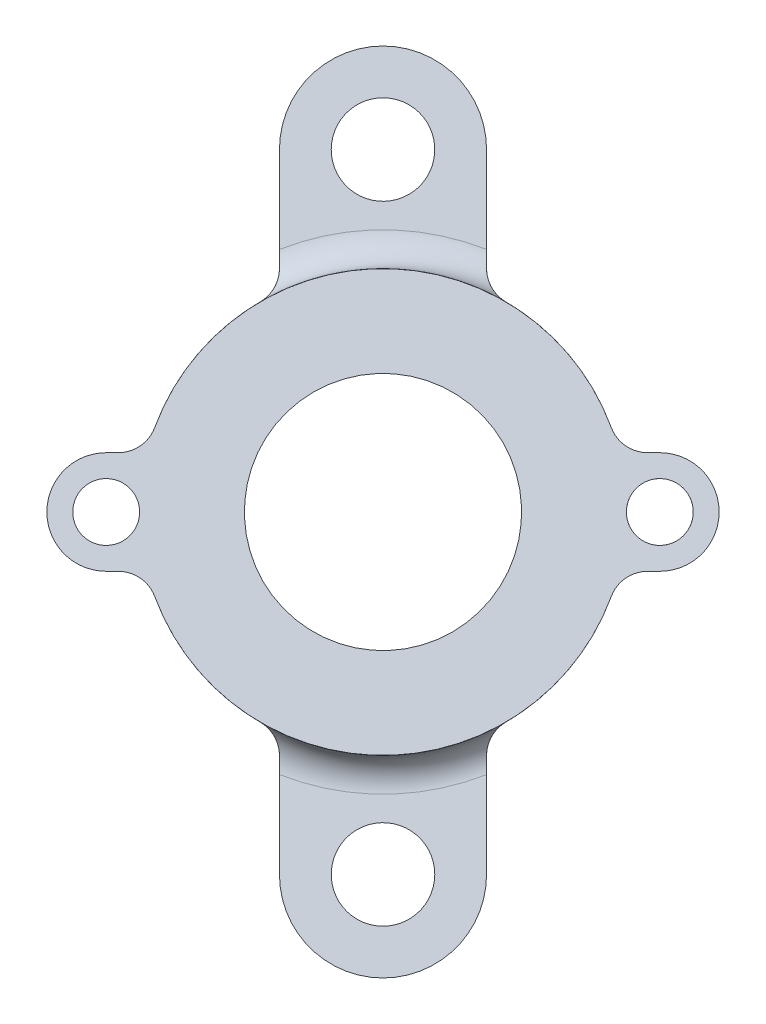
SolidWorks part; units mm, degrees
ref_plane "Front Plane" through (0, 0, 0) normal (0, 0, 1) x (1, 0, 0)
ref_plane "Top Plane" through (0, 0, 0) normal (0, 1, 0) x (1, 0, 0)
ref_plane "Right Plane" through (0, 0, 0) normal (1, 0, 0) x (0, 0, -1)
sketch "Sketch1" plane through (-73.1788, -73.1788, -73.1788) normal (0.5774, 0.5774, 0.5774) x (0.4082, 0.4082, -0.8165)
  circle A0 centre (0, 0) radius 5.875
  circle A3 centre (-11.1125, 0) radius 1.27 construction
  circle A4 centre (5.5563, -9.6237) radius 1.27 construction
  circle A5 centre (5.5562, 9.6237) radius 1.27 construction
  circle A6 centre (-11.1125, 0) radius 1.27
  circle A7 centre (5.5563, -9.6237) radius 1.27
  circle A8 centre (5.5562, 9.6237) radius 1.27
  dimension "D1" = 11.75
sketch "Sketch2" plane through (-79.4275, -79.4275, -79.4275) normal (0.5774, 0.5774, 0.5774) x (0.4082, 0.4082, -0.8165)
  circle A0 centre (0, 0) radius 5.875 construction
  circle A2 centre (0, 0) radius 5.875
ref_axis "Axis1" through (-79.4275, -79.4275, -79.4275) along (0.5774, 0.5774, 0.5774)
ref_plane "Plane1" through (0, 0, 0) normal (0, 0.7071, -0.7071) x (0.5774, 0.5774, 0.5774)
sketch "Sketch3" plane through (0, 0, 0) normal (0, 0.7071, -0.7071) x (0.5774, 0.5774, 0.5774)
  line L0 (-126.7493, 5.875) -> (-120.0724, 5.875)
  line L1 (-120.0724, 5.875) -> (-117.0724, 4.25)
  line L2 (-117.0724, 4.25) -> (-115.0724, 4.25)
  line L3 (-115.0724, 4.25) -> (-115.0724, 7.4625)
  line L4 (-126.7493, -5.875) -> (-126.7493, 5.875) construction
  line L6 (-126.7493, -5.875) -> (-126.7493, 5.875) construction
  line L7 (-137.5724, -5.875) -> (-137.5724, 5.875) construction
  line L8 (-137.5724, 0) -> (-126.7493, 0) construction
  line L9 (-115.0724, 7.4625) -> (-126.7493, 7.4625)
  line L10 (-126.7493, 7.4625) -> (-126.7493, 5.875)
  dimension "D1" = 17.5
  dimension "D2" = 4.25
  dimension "D3" = 3
  dimension "D4" = 2
  dimension "D5" = 1.5875
revolve "Revolve1" add sketch "Sketch3" angle 360 about axis through (-79.4275, -79.4275, -79.4275) along (0.5774, 0.5774, 0.5774)
sketch "Sketch4" plane through (-73.1788, -73.1788, -73.1788) normal (-0.5774, -0.5774, -0.5774) x (-0.4082, -0.4082, 0.8165)
  line L0 (-8.3059, 8.0362) -> (-6.1263, 4.2611)
  line L1 (-2.8066, 11.2112) -> (-0.6271, 7.4361)
  line L2 (-3.7313, 6.4627) -> (0, 0) construction
  line L3 (0, 0) -> (6.4627, 3.7312) construction
  line L4 (6.441, 5.8188) -> (5.3585, 5.1938)
  line L5 (5.3585, 5.1938) -> (7.1772, 2.0437)
  line L6 (7.1772, 2.0437) -> (8.2598, 2.6687)
  arc A0 (-2.8066, 11.2112) -> (-8.3059, 8.0362) centre (-5.5563, 9.6237) ccw
  circle A1 centre (-5.5563, 9.6237) radius 1.5875
  circle A2 centre (0, 0) radius 7.4625 construction
  arc A3 (-0.6271, 7.4361) -> (-6.1263, 4.2611) centre (0, 0) ccw
  arc A4 (-8.3059, 8.0362) -> (-2.8066, 11.2112) centre (-5.5563, 9.6237) ccw construction
  circle A5 centre (7.3504, 4.2437) radius 1.025
  arc A6 (6.441, 5.8188) -> (8.2598, 2.6687) centre (7.3504, 4.2437) cw
  circle M4 centre (0, 0) radius 7.4625
  dimension "D1" = 3.175
  dimension "D2" = 1.5875
  dimension "D4" = 2.05
  dimension "D5" = 0.7937
  dimension "D3" = 90
extrude "Boss-Extrude1" add sketch "Sketch4" against normal blind 3.175
extrude "Boss-Extrude3" add sketch "Sketch4<2>" against normal up to surface (11.6769 mm away) contours A6 L4 A5 L6 M4 | L5 M4 region at (-78.3602, -73.1788, -67.9974) region at (-79.4583, -71.739, -68.339) up to face at (-61.1603, -71.7139, -66.4371)
sketch "Sketch4<2>" plane through (-73.1788, -73.1788, -73.1788) normal (-0.5774, -0.5774, -0.5774) x (-0.4082, -0.4082, 0.8165) same geometry as "Sketch4"
fillet "Fillet1" radius 1.1906 5 edges at (-72.7742, -66.7481, -77.2643) (-77.2643, -66.7481, -72.7742) (-74.3922, -65.2526, -74.3922) (-74.1831, -71.2929, -63.9477) (-75.6681, -68.3229, -65.4327)
pattern_circular "CirPattern1" count 2 over 360 about axis through (-79.4275, -79.4275, -79.4275) along (0.5774, 0.5774, 0.5774) of "Boss-Extrude1", "Fillet1", "Boss-Extrude3"
ref_plane "Plane2" through (0, 0, 0) normal (0.7071, 0, -0.7071) x (-0.7071, 0, -0.7071)
